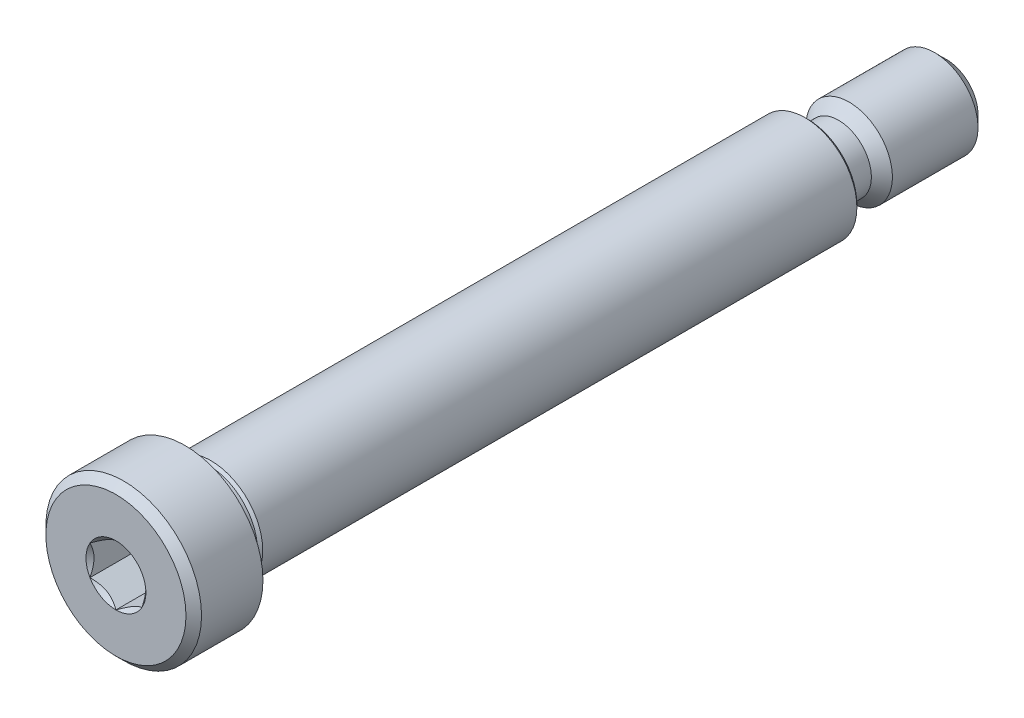
SolidWorks part; units mm, degrees
material "Alloy Steel"
ref_plane "Front Plane" through (0, 0, 0) normal (0, 0, 1) x (1, 0, 0)
ref_plane "Top Plane" through (0, 0, 0) normal (0, 1, 0) x (1, 0, 0)
ref_plane "Right Plane" through (0, 0, 0) normal (1, 0, 0) x (0, 0, -1)
sketch "Sketch2" plane through (0, 0, 0) normal (1, 0, 0) x (0, 0, -1)
  line L0 (-38.1, 0) -> (38.1, 0) construction
  line L1 (-38.1, 0) -> (-38.1, 7.1438)
  line L2 (-38.1, 7.1438) -> (-31.75, 7.1437)
  line L3 (-31.75, 7.1437) -> (-31.75, 4.7625)
  line L4 (-31.75, 4.7625) -> (25.4, 4.7625)
  line L5 (25.4, 3.9751) -> (38.1, 3.9751)
  line L6 (38.1, 3.9751) -> (38.1, 0)
  line L7 (38.0118, 4.1279) -> (38.7174, 2.9058) construction
  line L8 (38.7174, 2.9058) -> (39.4229, 4.1279) construction
  line L9 (39.4229, 4.1279) -> (38.0118, 4.1279) construction
  line L10 (38.1, 3.9751) -> (39.3347, 3.9751) construction
  line L11 (38.7174, 4.1279) -> (38.7174, 3.9751) construction
  line L12 (38.7174, 3.9751) -> (38.7174, 3.0586) construction
  line L13 (38.7174, 3.0586) -> (38.7174, 2.9058) construction
  line L14 (38.6292, 3.0586) -> (38.8056, 3.0586)
  line L15 (38.0559, 4.0515) -> (39.3788, 4.0515)
  line L16 (38.8056, 3.0586) -> (39.3788, 4.0515)
  line L17 (38.6292, 3.0586) -> (38.0559, 4.0515)
  line L18 (38.1, 0) -> (38.1, -3.9751) construction
  line L19 (25.4, -4.7625) -> (25.4, 0) construction
  line L20 (25.4, 0) -> (25.4, 4.7625) construction
  line L21 (-38.1, 0) -> (-38.1, -7.1438) construction
  point P11 (-29.3878, 4.7625)
  point P12 (34.5722, -3.9751)
  point P22 (38.7174, 4.0515)
  point P23 (19.685, 0)
  point P25 (-23.6728, 0)
  point P26 (-31.75, -7.1438)
  point P29 (25.4, -4.7625)
  dimension "Head Height" = 6.35
  dimension "Shoulder Diameter" = 9.525
  dimension "Screw Size Decimal Equivalent" = 7.9502
  dimension "Thread Length" = 12.7
  dimension "Head Diameter" = 14.2875
  dimension "Undercut Length" = 2.3622
  dimension "Pitch" = 1.4111
  dimension "D2" = 0.1764
  dimension "D1" = 3.5278
  dimension "Shoulder Length" = 57.15
  dimension "D4" = 5.715
  dimension "D3" = 5.715
sketch "Sketch3" plane through (0, 0, 0) normal (0, 0, 1) x (1, 0, 0)
  line L1 (0, 2.7496) -> (-2.3813, 1.3748)
  line L2 (-2.3813, 1.3748) -> (-2.3813, -1.3748)
  line L3 (-2.3813, -1.3748) -> (0, -2.7496)
  line L4 (0, -2.7496) -> (2.3812, -1.3748)
  line L5 (2.3812, -1.3748) -> (2.3812, 1.3748)
  line L6 (2.3812, 1.3748) -> (0, 2.7496)
  circle A0 centre (0, 0) radius 2.3813 construction
  dimension "Drive Size" = 4.7625
sketch "Sketch4" plane through (0, 0, 0) normal (1, 0, 0) x (0, 0, -1)
  line L0 (-31.75, 7.1437) -> (-37.3856, 7.1437)
  line L1 (-37.3856, 7.1437) -> (-38.1, 6.4294)
  line L2 (-31.75, 7.1437) -> (-31.75, 4.7625)
  line L3 (-31.75, 4.7625) -> (-31.5119, 4.5244)
  line L4 (-31.5119, 4.5244) -> (-29.6259, 4.5244)
  line L5 (-29.6259, 4.5244) -> (-29.3878, 4.7625)
  line L6 (-31.75, 4.7625) -> (25.4, 4.7625) construction
  line L7 (-38.1, 0) -> (38.1, 0) construction
  line L8 (-29.3878, 4.7625) -> (25.1375, 4.7625)
  line L9 (25.1375, 4.7625) -> (25.4, 4.5)
  line L10 (25.4, 4.5) -> (25.4, 0)
  line L11 (25.4, 4.7625) -> (25.4, 4.5) construction
  line L12 (25.4, 4.5) -> (25.4, 4.2376) construction
  line L13 (25.4, 4.2376) -> (25.4, 3.9751) construction
  line L14 (-38.1, 6.4294) -> (-38.1, 0)
  line L15 (-38.1, 7.1438) -> (-31.75, 7.1437) construction
  line L16 (-38.1, 0) -> (25.4, 0)
  dimension "D1" = 45
  dimension "D2" = 9.0487
  dimension "D3" = 45
  dimension "D4" = 45
  dimension "D5" = 12.8587
revolve "Revolve1" add sketch "Sketch4" angle 360 about L16
sketch "Sketch5" plane through (0, 0, 38.1) normal (0, 0, 1) x (1, 0, 0)
  line L0 (2.3812, 1.3748) -> (0, 2.7496) construction
  line L1 (2.3812, -1.3748) -> (2.3812, 1.3748) construction
  line L2 (0, -2.7496) -> (2.3812, -1.3748) construction
  line L3 (-2.3813, -1.3748) -> (0, -2.7496) construction
  line L4 (-2.3813, 1.3748) -> (-2.3813, -1.3748) construction
  line L5 (0, 2.7496) -> (-2.3813, 1.3748) construction
  line L6 (2.3812, 1.3748) -> (0, 2.7496)
  line L7 (2.3812, -1.3748) -> (2.3812, 1.3748)
  line L8 (0, -2.7496) -> (2.3812, -1.3748)
  line L9 (-2.3813, -1.3748) -> (0, -2.7496)
  line L10 (-2.3813, 1.3748) -> (-2.3813, -1.3748)
  line L11 (0, 2.7496) -> (-2.3813, 1.3748)
extrude "Cut-Extrude1" cut sketch "Sketch5" against normal blind 4.7625
sketch "Sketch6" plane through (0, 0, 38.1) normal (0, 0, 1) x (1, 0, 0)
  circle A0 centre (0, 0) radius 2.7496
extrude "Cut-Extrude4" cut sketch "Sketch6" against normal blind 4.7625 draft 45
sketch "Sketch7" plane through (0, 0, 0) normal (1, 0, 0) x (0, 0, -1)
  line L0 (25.4, 3.9751) -> (37.0417, 3.9751)
  line L1 (25.4, 3.9751) -> (38.1, 3.9751) construction
  line L2 (37.0417, 3.9751) -> (38.1, 2.9168)
  line L3 (38.1, 3.9751) -> (38.1, 0) construction
  line L4 (38.1, 2.9168) -> (38.1, 0)
  line L5 (38.1, 0) -> (25.4, 0)
  line L6 (25.4, -4.5) -> (25.4, 4.5) construction
  line L7 (25.4, 0) -> (25.4, 3.9751)
  dimension "D1" = 45
  dimension "D2" = 1.0583
revolve "Revolve2" add sketch "Sketch7" angle 360 about L5
sketch "Sketch10" plane through (0, 0, 0) normal (1, 0, 0) x (0, 0, -1)
  line L0 (26.3652, 3.0099) -> (28.2194, 3.0099)
  line L1 (28.2194, 3.0099) -> (29.972, 4.7625)
  line L2 (29.972, 4.7625) -> (25.4, 4.7625)
  line L3 (25.4, 4.7625) -> (25.4, 3.9751)
  line L4 (25.4, -4.5) -> (25.4, 4.5) construction
  line L5 (38.1, 0) -> (25.4, 0) construction
  line L6 (-38.1, 0) -> (38.1, 0) construction
  arc A0 (25.4, 3.9751) -> (26.3652, 3.0099) centre (26.3652, 3.9751) ccw
  dimension "Flat OD" = 6.0198
  dimension "Flat" = 2.8194
  dimension "D3" = 45
revolve "Cut-Revolve1" cut sketch "Sketch10" angle 360 about L5
sketch "Sketch8" [suppressed] plane through (0, 0, -38.1) normal (0, 0, -1) x (-1, 0, 0)
  circle A0 centre (0, 0) radius 3.9751 construction
  circle A1 centre (0, 0) radius 3.9751
curve "Helix/Spiral1" [suppressed] pitch 1.4111 height 14.1111 turns 10
sketch "Sketch9" [suppressed] plane through (0, 0, 0) normal (1, 0, 0) x (0, 0, -1)
  line L0 (38.6292, 3.0586) -> (38.8056, 3.0586) construction
  line L1 (38.8056, 3.0586) -> (39.3788, 4.0515) construction
  line L2 (38.0559, 4.0515) -> (39.3788, 4.0515) construction
  line L3 (38.6292, 3.0586) -> (38.0559, 4.0515) construction
  line L4 (38.6292, 3.0586) -> (38.8056, 3.0586)
  line L5 (38.8056, 3.0586) -> (39.3788, 4.0515)
  line L6 (38.0559, 4.0515) -> (39.3788, 4.0515)
  line L7 (38.6292, 3.0586) -> (38.0559, 4.0515)
ref_plane "Plane1" [suppressed] through (0, 0, -28.2194) normal (0, 0, 1) x (1, 0, 0)
split "Split1" [suppressed] bodies to split 138
sweep "Cut-Sweep1" [suppressed] cut profiles "Sketch9" path "Helix/Spiral1"
combine bodies "Combine1" [suppressed] operation type add bodies to combine 141 139
sketch "Sketch11" [suppressed] plane through (0, 0, 38.1) normal (0, 0, 1) x (1, 0, 0)
  line L0 (-0.1031, 7.1437) -> (0.1031, 7.1437)
  line L1 (0.1031, 7.1437) -> (0, 6.9652)
  line L2 (0, 0) -> (0, 7.1438) construction
  line L3 (0, 6.9652) -> (-0.1031, 7.1437)
  line L4 (0, 0) -> (7.1437, 0) construction
  circle A0 centre (0, 0) radius 7.1437 construction
  point P6 (0, 7.1437)
  dimension "D1" = 13.9303
  dimension "D2" = 60
  dimension "D3" = 0.2062
sketch "Sketch12" [suppressed] plane through (0, 0, 0) normal (1, 0, 0) x (0, 0, -1)
  line L0 (-38.1, 6.9652) -> (-33.7687, 6.9652)
  line L1 (-33.1589, 7.5749) -> (-33.1589, 7.1438) construction
  line L2 (-38.1, 7.1438) -> (-31.75, 7.1438) construction
  arc A0 (-33.7687, 6.9652) -> (-33.1589, 7.5749) centre (-33.7687, 7.5749) ccw
  point P11 (-33.3375, 7.1438)
  dimension "D1" = 1.5875
sweep "Cut-Sweep2" [suppressed] cut profiles "Sketch11" path "Sketch12"
pattern_circular "CirPattern1" [suppressed] count 76 over 360 about axis through (0, 0, 38.1) along (0, 0, -1) of bodies 143
equation "\"D2@Sketch2\" = \"Pitch@Sketch2\" / 8"
equation "\"D1@Sketch2\"=\"Pitch@Sketch2\"*2.5"
equation "\"D2@Sketch4\"=\"Shoulder Diameter@Sketch2\"*0.95"
equation "\"D5@Sketch4\"=\"Head Diameter@Sketch2\"*0.9"
equation "\"D1@Cut-Extrude1\"=\"Head Height@Sketch2\"*0.75"
equation "\"D1@Cut-Extrude4\"=\"D1@Cut-Extrude1\""
equation "\"D2@Sketch7\"=\"pitch@sketch2\"*0.75"
equation "\"D3@Helix/Spiral1\"=\"Thread Length@Sketch2\"+\"Pitch@Sketch2\""
equation "\"D4@Helix/Spiral1\"=\"Pitch@Sketch2\""
equation "\"D1@Sketch11\"=\"Head Diameter@Sketch2\"*0.975"
equation "\"D1@Sketch12\"=\"Head Height@Sketch2\"*0.25"
equation "\"D1@CirPattern1\"=\"Head Diameter@Sketch2\" * 3.14 / \"D3@Sketch11\" * 0.35"
equation "\"D3@Sketch2\"=\"D4@Sketch2\""
equation "\"D4@Sketch2\"=IF(\"Shoulder Length@Sketch2\"<.5,.1,(\"Shoulder Length@Sketch2\"*.1))"
